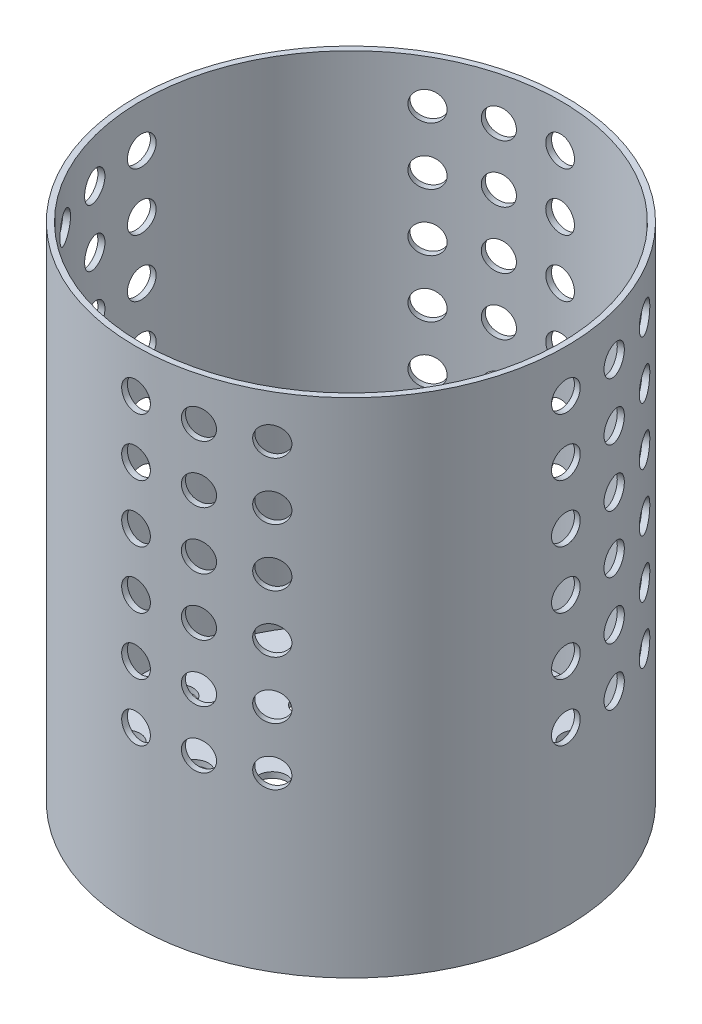
SolidWorks part; units mm, degrees
ref_plane "Front Plane" through (0, 0, 0) normal (0, 0, 1) x (1, 0, 0)
ref_plane "Top Plane" through (0, 0, 0) normal (0, 1, 0) x (1, 0, 0)
ref_plane "Right Plane" through (0, 0, 0) normal (1, 0, 0) x (0, 0, -1)
sketch "Sketch1" plane through (0, 0, 0) normal (0, 1, 0) x (1, 0, 0)
  circle A0 centre (0, 0) radius 75
  dimension "D1" = 150
extrude "Boss-Extrude1" add sketch "Sketch1" along normal blind 175
shell "Shell1" thickness 2 removed face at (0, 175, 75)
ref_plane "Plane1" through (75, 0, 0) normal (1, 0, 0) x (0, 0, -1)
sketch "Sketch2" plane through (75, 0, 0) normal (1, 0, 0) x (0, 0, -1)
  line L0 (73, 175) -> (-73, 175) construction
  circle A0 centre (0, 160) radius 5
  circle A1 centre (0, 140) radius 5
  circle A2 centre (0, 120) radius 5
  circle A3 centre (0, 100) radius 5
  circle A4 centre (0, 80) radius 5
  circle A5 centre (0, 60) radius 5
  dimension "D1" = 10
  dimension "D2" = 15
  dimension "D3" = 6
extrude "Cut-Extrude1" cut sketch "Sketch2" against normal blind 25
pattern_circular "CirPattern1" count 3 every 15 about axis through (0, 175, 0) along (0, 1, 0) of "Cut-Extrude1"
pattern_circular "CirPattern2" count 4 over 360 about axis through (0, 175, 0) along (0, -1, 0) of "CirPattern1"
sketch "Sketch3" plane through (0, 0, 0) normal (0, -1, 0) x (1, 0, 0)
  circle A0 centre (0, 0) radius 5
  circle A1 centre (0, 0) radius 20 construction
  circle A2 centre (0, 0) radius 60 construction
  circle A3 centre (0, 0) radius 40 construction
  circle A4 centre (0, 20) radius 5
  circle A5 centre (0, 40) radius 5
  circle A6 centre (0, 60) radius 5
  circle A7 centre (17.3205, 10) radius 5
  circle A8 centre (17.3205, -10) radius 5
  circle A9 centre (0, -20) radius 5
  circle A10 centre (-17.3205, -10) radius 5
  circle A11 centre (-17.3205, 10) radius 5
  circle A12 centre (20, 34.641) radius 5
  circle A13 centre (34.641, 20) radius 5
  circle A14 centre (40, 0) radius 5
  circle A15 centre (34.641, -20) radius 5
  circle A16 centre (20, -34.641) radius 5
  circle A17 centre (0, -40) radius 5
  circle A18 centre (-20, -34.641) radius 5
  circle A19 centre (-34.641, -20) radius 5
  circle A20 centre (-40, 0) radius 5
  circle A21 centre (-34.641, 20) radius 5
  circle A22 centre (-20, 34.641) radius 5
  circle A23 centre (22.961, 55.4328) radius 5
  circle A24 centre (42.4264, 42.4264) radius 5
  circle A25 centre (55.4328, 22.961) radius 5
  circle A26 centre (60, 0) radius 5
  circle A27 centre (55.4328, -22.961) radius 5
  circle A28 centre (42.4264, -42.4264) radius 5
  circle A29 centre (22.961, -55.4328) radius 5
  circle A30 centre (0, -60) radius 5
  circle A31 centre (-22.961, -55.4328) radius 5
  circle A32 centre (-42.4264, -42.4264) radius 5
  circle A33 centre (-55.4328, -22.961) radius 5
  circle A34 centre (-60, 0) radius 5
  circle A35 centre (-55.4328, 22.961) radius 5
  circle A36 centre (-42.4264, 42.4264) radius 5
  circle A37 centre (-22.961, 55.4328) radius 5
  point P24 (0, 0)
  point P47 (0, 0)
  point P78 (0, 0)
  dimension "D1" = 40
  dimension "D2" = 10
  dimension "D3" = 80
  dimension "D4" = 120
  dimension "D5" = 6
  dimension "D6" = 12
  dimension "D7" = 16
extrude "Cut-Extrude2" cut sketch "Sketch3" against normal blind 25
